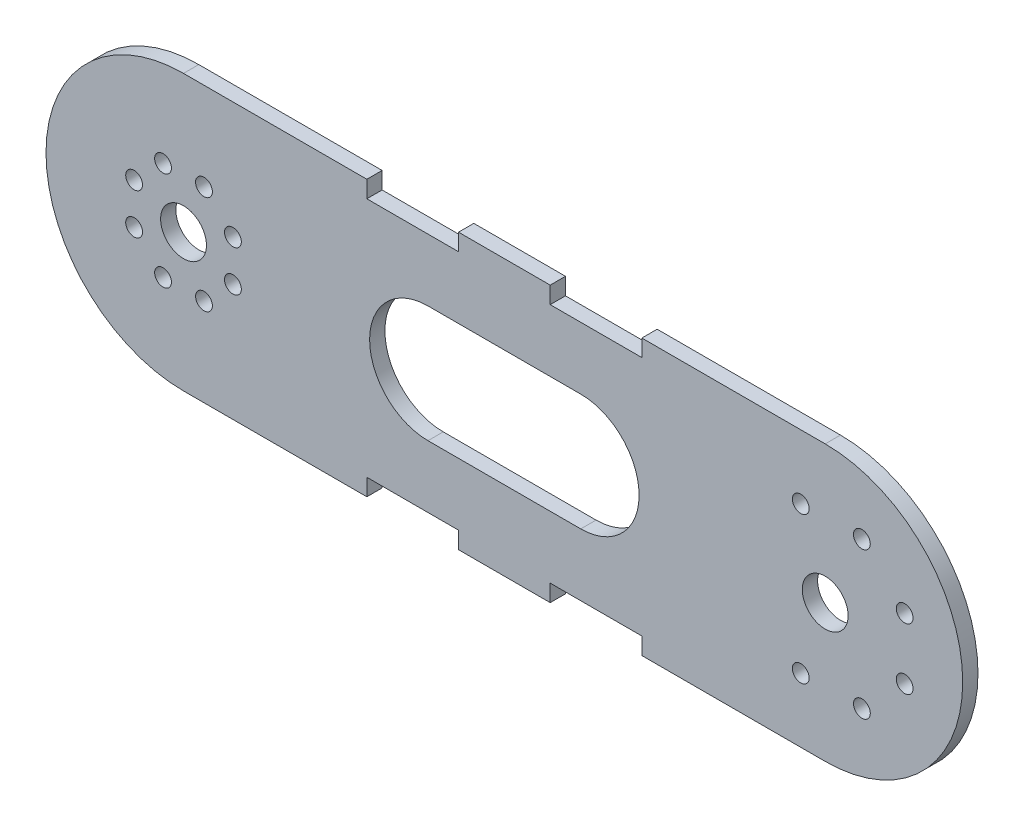
SolidWorks part; units mm, degrees
ref_plane "Front Plane" through (0, 0, 0) normal (0, 0, 1) x (1, 0, 0)
ref_plane "Top Plane" through (0, 0, 0) normal (0, 1, 0) x (1, 0, 0)
ref_plane "Right Plane" through (0, 0, 0) normal (1, 0, 0) x (0, 0, -1)
sketch "Sketch3" plane through (0, 0, 0) normal (0, 0, 1) x (1, 0, 0)
  line L0 (-20.9627, 0) -> (189.0373, 0) construction
  line L1 (-20.9627, 45) -> (189.0373, 45)
  line L2 (-20.9627, -45) -> (189.0373, -45)
  line L3 (59.0373, 0) -> (109.0373, 0) construction
  line L4 (59.0373, 19.0946) -> (109.0373, 19.0946)
  line L5 (59.0373, -19.0946) -> (109.0373, -19.0946)
  line L6 (39.0373, -45) -> (39.0373, -39.46)
  line L9 (-20.9627, 0) -> (-4.7949, 6.697)
  line L10 (-20.9627, 0) -> (-4.7949, 6.697) construction
  line L11 (-20.9627, 0) -> (-4.7949, -6.697) construction
  line L13 (99.0373, -45) -> (129.0373, -45)
  line L14 (99.0373, -45) -> (99.0373, -39.46)
  line L15 (99.0373, -39.46) -> (129.0373, -39.46)
  line L16 (129.0373, -45) -> (129.0373, -39.46)
  line L36 (-101.4371, 0) -> (436.7316, 0) construction
  line L53 (39.0373, -45) -> (69.0373, -45)
  line L54 (69.0373, -45) -> (69.0373, -39.46)
  line L55 (39.0373, -39.46) -> (69.0373, -39.46)
  line L56 (99.0373, 39.46) -> (129.0373, 39.46)
  line L57 (129.0373, 45) -> (129.0373, 39.46)
  line L58 (99.0373, 45) -> (129.0373, 45)
  line L59 (99.0373, 45) -> (99.0373, 39.46)
  line L60 (39.0373, 45) -> (69.0373, 45)
  line L61 (69.0373, 45) -> (69.0373, 39.46)
  line L62 (39.0373, 39.46) -> (69.0373, 39.46)
  line L63 (39.0373, 45) -> (39.0373, 39.46)
  arc A0 (-20.9627, 45) -> (-20.9627, -45) centre (-20.9627, 0) ccw
  arc A1 (189.0373, -45) -> (189.0373, 45) centre (189.0373, 0) ccw
  circle A2 centre (-20.9627, 0) radius 7.5
  circle A3 centre (189.0373, 0) radius 7.5
  arc A4 (59.0373, 19.0946) -> (59.0373, -19.0946) centre (59.0373, 0) ccw
  arc A5 (109.0373, -19.0946) -> (109.0373, 19.0946) centre (109.0373, 0) ccw
  circle A8 centre (-4.7949, 6.697) radius 2.75
  circle A9 centre (-4.7949, -6.697) radius 2.75
  circle A10 centre (-14.2658, -16.1679) radius 2.75
  circle A11 centre (-27.6597, -16.1679) radius 2.75
  circle A12 centre (-37.1306, -6.697) radius 2.75
  circle A13 centre (-37.1306, 6.697) radius 2.75
  circle A14 centre (-27.6597, 16.1679) radius 2.75
  circle A15 centre (-14.2658, 16.1679) radius 2.75
  circle A16 centre (215.0373, 10) radius 2.75
  circle A17 centre (201.0373, 24) radius 2.75
  circle A18 centre (181.0373, 24) radius 2.75
  circle A19 centre (215.0373, -10) radius 2.75
  circle A20 centre (201.0373, -24) radius 2.75
  circle A21 centre (181.0373, -24) radius 2.75
  point P3 (84.0373, 0)
  point P14 (84.0373, 0)
  dimension "D2" = 45
  dimension "D3" = 15
  dimension "D4" = 15
  dimension "D7" = 5.5
  dimension "D21" = 5.5
  dimension "D22" = 5.5
  dimension "D23" = 5.5
  dimension "D1" = 210
  dimension "D5" = 17.5
  dimension "D6" = 22.5
  dimension "D9" = 45
  dimension "D10" = 5.54
  dimension "D11" = 30
  dimension "D12" = 45
  dimension "D15" = 24
  dimension "D16" = 24
  dimension "D17" = 8
  dimension "D18" = 20
  dimension "D19" = 26
  dimension "D20" = 10
  dimension "D24" = 50
  dimension "D25" = 0
  dimension "D13" = 2
  dimension "D8" = 8
extrude "Boss-Extrude1" add sketch "Sketch3" along normal blind 5 contours L2 A1 L1 A0 L60 L14 L15 L16 region at (9.0373, 41.8679, 0)
